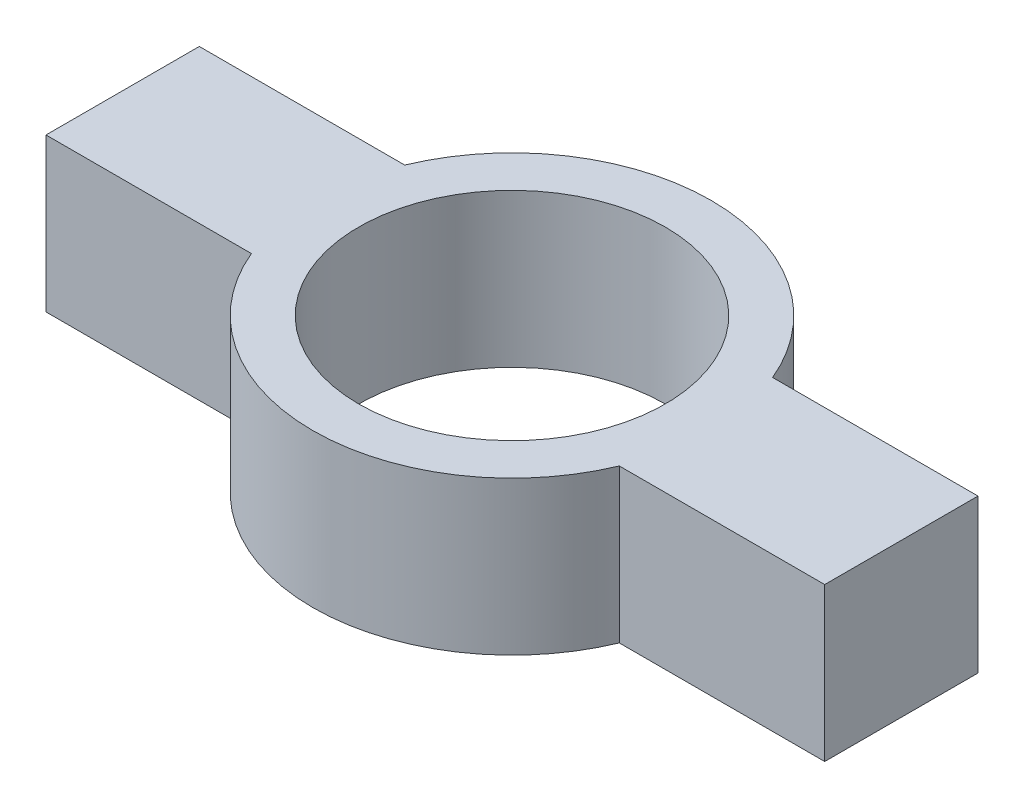
SolidWorks part; units mm, degrees
ref_plane "Front Plane" through (0, 0, 0) normal (0, 0, 1) x (1, 0, 0)
ref_plane "Top Plane" through (0, 0, 0) normal (0, 1, 0) x (1, 0, 0)
ref_plane "Right Plane" through (0, 0, 0) normal (1, 0, 0) x (0, 0, -1)
sketch "Sketch1" plane through (0, 0, 0) normal (0, 1, 0) x (1, 0, 0)
  circle A0 centre (0, 0) radius 5
  circle A1 centre (0, 0) radius 6.5
  dimension "D1" = 10
  dimension "D2" = 1.5
extrude "Boss-Extrude1" add sketch "Sketch1" along normal blind 5
ref_axis "Axis1" through (0, 5, 0) along (0, -1, 0)
ref_plane "Plane1" through (0, 0, 0) normal (-1, 0, 0) x (0, -1, 0)
sketch "Sketch2" plane through (0, 0, 0) normal (-1, 0, 0) x (0, -1, 0)
  line L0 (-5.0337, 0) -> (0, 0) construction
  line L1 (-5, 0) -> (0, 0) construction
  line L2 (-2.5, 6.5) -> (-2.5, -6.5) construction
  line L3 (0, 6.5) -> (-5, 6.5) construction
  line L4 (-5, -6.5) -> (0, -6.5) construction
  line L5 (-5, 6.5) -> (-5, -6.5) construction
  line L6 (-5, 2.5) -> (0, 2.5)
  line L7 (-5, 2.5) -> (-5, -2.5)
  line L8 (-5, -2.5) -> (0, -2.5)
  line L9 (0, 2.5) -> (0, -2.5)
  line L10 (0, -6.5) -> (0, 6.5) construction
  dimension "D1" = 5
  dimension "D2" = 2.5
extrude "Boss-Extrude2" add sketch "Sketch2" along normal mid plane 25.4
sketch "Sketch3" plane through (0, 5, 0) normal (0, 1, 0) x (1, 0, 0)
  circle A0 centre (0, 0) radius 5
extrude "Cut-Extrude1" cut sketch "Sketch3" against normal through all
